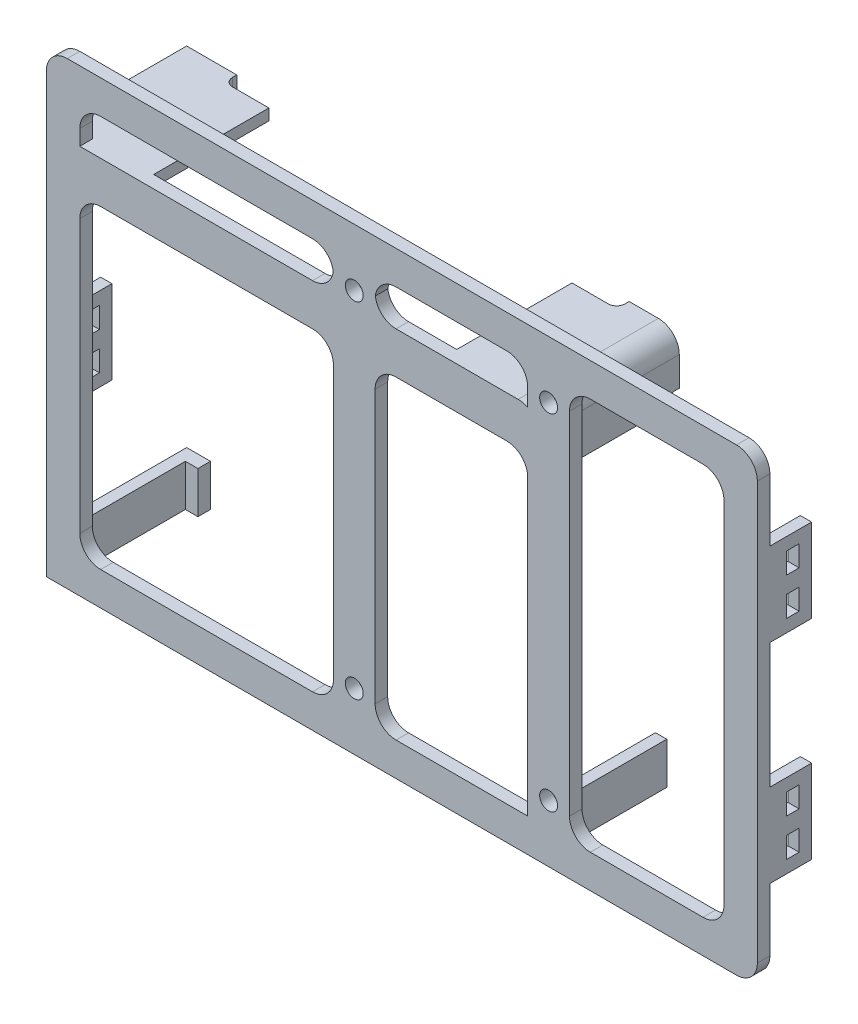
SolidWorks part; units mm, degrees
ref_plane "Front Plane" through (0, 0, 0) normal (0, 0, 1) x (1, 0, 0)
ref_plane "Top Plane" through (0, 0, 0) normal (0, 1, 0) x (1, 0, 0)
ref_plane "Right Plane" through (0, 0, 0) normal (1, 0, 0) x (0, 0, -1)
sketch "Sketch1" plane through (0, 0, 0) normal (0, 0, 1) x (1, 0, 0)
  line L0 (115.3, 20) -> (125.3, 20) construction
  line L1 (0, 0) -> (170.3, 0)
  line L2 (0, 0) -> (0, 110)
  line L3 (0, 110) -> (170.3, 110)
  line L4 (170.3, 0) -> (170.3, 110)
  line L5 (8, 8) -> (68.75, 8)
  line L6 (8, 8) -> (8, 83.3)
  line L7 (8, 102) -> (68.75, 102)
  line L8 (162.3, 8) -> (162.3, 102)
  line L9 (115.3, 83.3) -> (115.3, 8)
  line L10 (8, 83.3) -> (68.75, 83.3)
  line L11 (115.3, 102) -> (115.3, 93.3)
  line L12 (68.75, 8) -> (68.75, 83.3)
  line L13 (125.3, 8) -> (125.3, 102)
  line L14 (125.3, 102) -> (162.3, 102)
  line L15 (125.3, 8) -> (162.3, 8)
  line L16 (162.3, 102) -> (170.3, 102) construction
  line L17 (8, 93.3) -> (68.75, 93.3)
  line L18 (8, 93.3) -> (8, 102)
  line L19 (78.75, 8) -> (78.75, 83.3)
  line L20 (78.75, 8) -> (115.3, 8)
  line L21 (78.75, 83.3) -> (115.3, 83.3)
  line L22 (68.75, 83.3) -> (78.75, 83.3) construction
  line L23 (68.75, 93.3) -> (68.75, 102)
  line L24 (78.75, 93.3) -> (78.75, 102)
  line L25 (78.75, 93.3) -> (115.3, 93.3)
  line L26 (78.75, 102) -> (115.3, 102)
  point P4 (120.3, 20)
  point P25 (73.75, 83.3)
  dimension "D1" = 110
  dimension "D2" = 10
  dimension "D3" = 8
  dimension "D4" = 8
  dimension "D5" = 8
  dimension "D6" = 8
  dimension "D7" = 50
  dimension "D8" = 10
  dimension "D9" = 115.3
  dimension "D10" = 18.7
  dimension "D11" = 20
  dimension "D12" = 10
  dimension "D13" = 46.55
extrude "Boss-Extrude1" add sketch "Sketch1" along normal blind 3
hole_wizard "#6 Clearance Hole1" positions "Sketch4" profile "Sketch5" hole size "#6" standard "ANSI Inch" end condition through all
sketch "Sketch4" plane through (0, 0, 0) normal (0, 0, -1) x (-1, 0, 0)
  line L13 (-170.3, 0) -> (-170.3, 110) construction
  line L14 (-120.3, 13.725) -> (-120.3, 96.275) construction
  line L16 (-115.3, 8) -> (-125.3, 8) construction
  line L17 (-68.75, 8) -> (-78.75, 8) construction
  line L19 (-73.75, 13.725) -> (-73.75, 96.275) construction
  point P0 (-120.3, 13.725)
  point P2 (-120.3, 96.275)
  point P56 (-170.3, 55)
  point P67 (-120.3, 55)
  point P68 (-120.3, 8)
  point P70 (-73.75, 13.725)
  point P72 (-73.75, 96.275)
  point P86 (-73.75, 8)
  dimension "D1" = 82.55
sketch "Sketch5" plane through (120.3, 13.725, 0) normal (1, 0, 0) x (0, 1, 0)
  line L0 (0, 0) -> (0, 3)
  line L1 (0, 3) -> (2.1526, 3)
  line L2 (2.1526, 3) -> (2.1526, 0)
  line L5 (2.1526, 0) -> (0, 0)
  line L11 (0, -6.35) -> (0, 107.95) construction
  dimension "Thru Hole Dia." = 4.3053
  dimension "Thru Hole Depth" = 3
sketch "Sketch6" plane through (0, 0, 0) normal (0, 0, -1) x (-1, 0, 0)
  line L0 (0, 0) -> (-170.3, 0) construction
  line L3 (0, 0) -> (-2.7, 0)
  line L4 (0, 0) -> (0, 10)
  line L5 (0, 10) -> (-2.7, 10)
  line L6 (-2.7, 0) -> (-2.7, 10)
  line L7 (-115.3, 0) -> (-118, 0)
  line L8 (-115.3, 0) -> (-115.3, 10)
  line L9 (-115.3, 10) -> (-118, 10)
  line L10 (-118, 0) -> (-118, 10)
  line L11 (0, 81.3) -> (0, 93.3)
  line L13 (0, 110) -> (0, 0) construction
  line L14 (0, 93.3) -> (-22.7, 93.3)
  line L16 (-22.7, 93.3) -> (-22.7, 90.6)
  line L17 (-22.7, 90.6) -> (-2.7, 90.6)
  line L19 (-2.7, 90.6) -> (-2.7, 81.3)
  line L20 (-2.7, 81.3) -> (0, 81.3)
  line L21 (-95.3, 93.3) -> (-118, 93.3)
  line L22 (-118, 93.3) -> (-118, 78.6)
  line L24 (-118, 78.6) -> (-115.3, 78.6)
  line L25 (-115.3, 8) -> (-115.3, 83.3) construction
  line L26 (-115.3, 78.6) -> (-115.3, 90.6)
  line L27 (-115.3, 90.6) -> (-95.3, 90.6)
  line L28 (-95.3, 90.6) -> (-95.3, 93.3)
  dimension "D1" = 10
  dimension "D2" = 2.7
  dimension "D3" = 2.7
  dimension "D4" = 2.7
  dimension "D5" = 20
  dimension "D6" = 90.6
  dimension "D7" = 12
  dimension "D8" = 90.6
  dimension "D9" = 2.7
  dimension "D10" = 20
  dimension "D11" = 12
  dimension "D12" = 10
  dimension "D13" = 2.7
extrude "Boss-Extrude2" add sketch "Sketch6" along normal blind 27.6
sketch "Sketch7" plane through (0, 0, -27.6) normal (0, 0, -1) x (-1, 0, 0)
  line L1 (-115.3, 78.6) -> (-115.3, 90.6) construction
  line L2 (0, 93.3) -> (0, 81.3)
  line L3 (-115.3, 90.6) -> (-95.3, 90.6) construction
  line L4 (0, 0) -> (-5.7, 0)
  line L5 (0, 0) -> (0, 10)
  line L6 (0, 10) -> (-5.7, 10)
  line L7 (-5.7, 0) -> (-5.7, 10)
  line L8 (0, 81.3) -> (-5.7, 81.3)
  line L9 (-5.7, 81.3) -> (-5.7, 87.6)
  line L10 (-5.7, 87.6) -> (-12, 87.6)
  line L11 (-12, 87.6) -> (-12, 93.3)
  line L12 (-22.7, 90.6) -> (-2.7, 90.6) construction
  line L13 (0, 93.3) -> (-8, 93.3) construction
  line L17 (-12, 93.3) -> (0, 93.3)
  line L18 (-118, 93.3) -> (-118, 81.3)
  line L22 (-118, 93.3) -> (-118, 78.6) construction
  line L23 (-118, 81.3) -> (-112.3, 81.3)
  line L24 (-112.3, 81.3) -> (-112.3, 87.6)
  line L25 (-112.3, 87.6) -> (-106, 87.6)
  line L26 (-106, 87.6) -> (-106, 93.3)
  line L27 (-95.3, 93.3) -> (-78.75, 93.3) construction
  line L28 (-106, 93.3) -> (-118, 93.3)
  line L29 (-2.7, 10) -> (-2.7, 0) construction
  line L30 (-2.7, 90.6) -> (-2.7, 81.3) construction
  dimension "D1" = 10
  dimension "D2" = 3
  dimension "D3" = 3
  dimension "D4" = 3
  dimension "D5" = 3
  dimension "D6" = 12
  dimension "D7" = 12
  dimension "D8" = 3
  dimension "D9" = 12
extrude "Boss-Extrude3" add sketch "Sketch7" along normal blind 3
fillet "Fillet3" radius 5 1 edges at (118, 93.3, -15.3)
fillet "Fillet4" radius 2 3 edges at (116.65, 81.3, -27.6) (106, 91.95, -27.6) (12, 91.95, -27.6)
fillet "Fillet5" radius 5 20 edges at (8, 8, 1.5) (8, 83.3, 1.5) (125.3, 8, 1.5) (162.3, 8, 1.5) (162.3, 102, 1.5) (125.3, 102, 1.5) (8, 102, 1.5) (170.3, 0, 1.5) (170.3, 110, 1.5) (0, 110, 1.5) (115.3, 102, 1.5) (78.75, 102, 1.5) (78.75, 93.3, 1.5) (68.75, 102, 1.5) (68.75, 93.3, 1.5) (68.75, 8, 1.5) (78.75, 8, 1.5) (78.75, 83.3, 1.5) (68.75, 83.3, 1.5) (115.3, 83.3, 1.5)
sketch "Sketch8" plane through (0, 0, 0) normal (0, 0, -1) x (-1, 0, 0)
  line L0 (0, 81.3) -> (0, 10) construction
  line L1 (-2.7, 35.65) -> (0, 35.65)
  line L2 (-2.7, 35.65) -> (-2.7, 55.65)
  line L3 (-2.7, 55.65) -> (0, 55.65)
  line L4 (0, 35.65) -> (0, 55.65)
  point P4 (0, 45.65)
  point P7 (0, 45.65)
  dimension "D1" = 20
  dimension "D2" = 2.7
extrude "Boss-Extrude4" add sketch "Sketch8" along normal blind 10
sketch "Sketch9" plane through (0, 0, 0) normal (-1, 0, 0) x (0, 0, 1)
  line L0 (-7, 43.65) -> (-7, 47.65) construction
  line L1 (-7, 38.65) -> (-4, 38.65)
  line L2 (-7, 38.65) -> (-7, 43.65)
  line L3 (-7, 43.65) -> (-4, 43.65)
  line L4 (-4, 38.65) -> (-4, 43.65)
  line L5 (-7, 47.65) -> (-4, 47.65)
  line L6 (-7, 47.65) -> (-7, 52.65)
  line L7 (-7, 52.65) -> (-4, 52.65)
  line L8 (-4, 47.65) -> (-4, 52.65)
  line L9 (-10, 35.65) -> (-10, 55.65) construction
  line L10 (-10, 35.65) -> (0, 35.65) construction
  point P8 (-7, 45.65)
  point P11 (-10, 45.65)
  dimension "D1" = 5
  dimension "D2" = 5
  dimension "D3" = 3
  dimension "D4" = 3
  dimension "D5" = 3
  dimension "D6" = 3
extrude "Cut-Extrude1" cut sketch "Sketch9" against normal blind 3 and the other way through all
sketch "Sketch11" plane through (0, 0, 0) normal (0, 0, -1) x (-1, 0, 0)
  line L0 (-170.3, 70) -> (-170.3, 40) construction
  line L1 (-167.6, 20) -> (-170.3, 20)
  line L2 (-167.6, 20) -> (-167.6, 40)
  line L3 (-167.6, 40) -> (-170.3, 40)
  line L4 (-170.3, 20) -> (-170.3, 40)
  line L5 (-167.6, 70) -> (-170.3, 70)
  line L6 (-167.6, 70) -> (-167.6, 90)
  line L7 (-167.6, 90) -> (-170.3, 90)
  line L8 (-170.3, 70) -> (-170.3, 90)
  line L9 (-170.3, 5) -> (-170.3, 105) construction
  line L10 (-118, 0) -> (-165.3, 0) construction
  point P8 (-170.3, 55)
  point P11 (-170.3, 55)
  dimension "D1" = 2.7
  dimension "D2" = 20
  dimension "D3" = 20
extrude "Boss-Extrude5" add sketch "Sketch11" along normal blind 10
sketch "Sketch12" plane through (170.3, 0, 0) normal (1, 0, 0) x (0, 0, -1)
  line L0 (7, 82) -> (7, 78) construction
  line L1 (7, 37) -> (4, 37)
  line L2 (7, 37) -> (7, 32)
  line L3 (7, 32) -> (4, 32)
  line L4 (4, 37) -> (4, 32)
  line L5 (7, 28) -> (4, 28)
  line L6 (7, 28) -> (7, 23)
  line L7 (7, 23) -> (4, 23)
  line L8 (4, 28) -> (4, 23)
  line L9 (7, 87) -> (4, 87)
  line L10 (7, 87) -> (7, 82)
  line L11 (7, 82) -> (4, 82)
  line L12 (4, 87) -> (4, 82)
  line L13 (7, 78) -> (4, 78)
  line L14 (7, 78) -> (7, 73)
  line L15 (7, 73) -> (4, 73)
  line L16 (4, 78) -> (4, 73)
  line L17 (7, 32) -> (7, 28) construction
  line L18 (10, 90) -> (10, 70) construction
  line L19 (10, 40) -> (10, 20) construction
  line L20 (10, 90) -> (0, 90) construction
  line L21 (10, 20) -> (0, 20) construction
  point P16 (7, 80)
  point P19 (10, 80)
  point P20 (7, 30)
  point P23 (10, 30)
  dimension "D1" = 3
  dimension "D2" = 3
  dimension "D3" = 5
  dimension "D4" = 3
  dimension "D5" = 3
  dimension "D6" = 3
extrude "Cut-Extrude2" cut sketch "Sketch12" against normal blind 3
